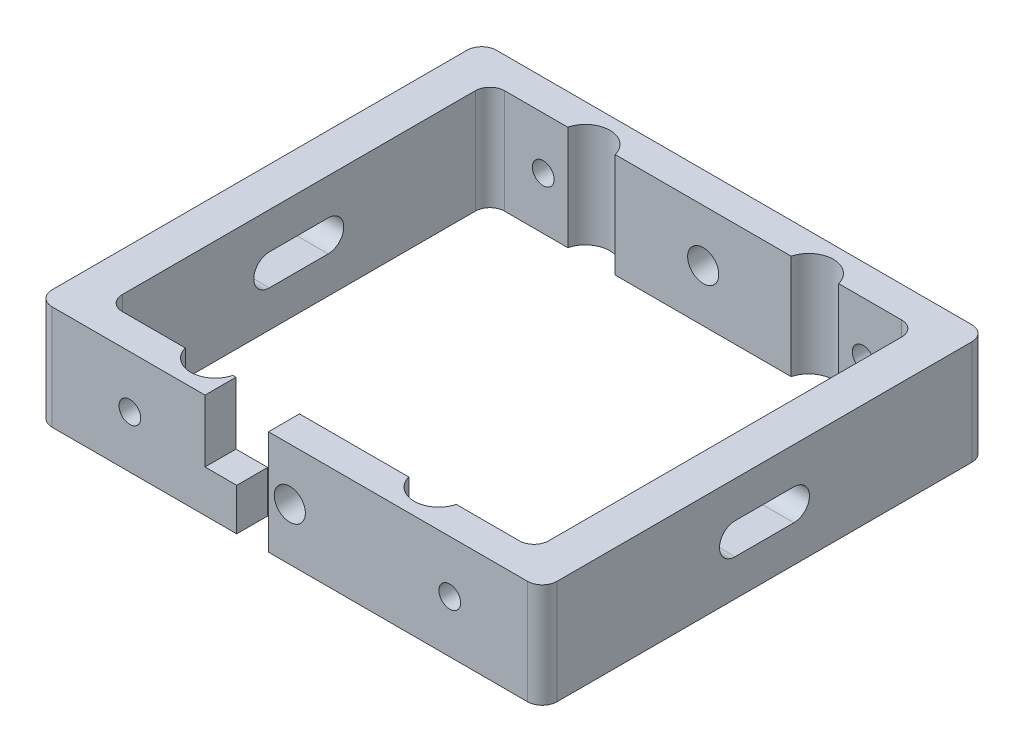
SolidWorks part; units mm, degrees
ref_plane "Front Plane" through (0, 0, 0) normal (0, 0, 1) x (1, 0, 0)
ref_plane "Top Plane" through (0, 0, 0) normal (0, 1, 0) x (1, 0, 0)
ref_plane "Right Plane" through (0, 0, 0) normal (1, 0, 0) x (0, 0, -1)
sketch "Sketch1" plane through (0, 0, 0) normal (0, 1, 0) x (1, 0, 0)
  line L1 (0, 0) -> (60, 0)
  line L2 (0, 0) -> (0, -6.32)
  line L3 (0, -6.32) -> (60, -6.32)
  line L4 (60, 0) -> (60, -6.32)
  dimension "D1" = 60
  dimension "D2" = 6.32
extrude "Boss-Extrude1" add sketch "Sketch1" along normal mid plane 21.28
sketch "Sketch2" plane through (0, 10.64, 0) normal (0, 1, 0) x (1, 0, 0)
  line L0 (0, 0) -> (0, -6.32) construction
  line L1 (0, -6.32) -> (60, -6.32) construction
  line L2 (60, -6.32) -> (60, 0) construction
  circle A0 centre (7.21, 1.25) radius 5
  circle A1 centre (52.79, 1.25) radius 5
  dimension "D1" = 7.21
  dimension "D3" = 7.21
  dimension "D2" = 7.57
  dimension "D4" = 7.57
extrude "Cut-Extrude1" cut sketch "Sketch2" against normal through all
sketch "Sketch3" plane through (60, 0, 0) normal (1, 0, 0) x (0, 0, -1)
  line L1 (-6.32, 10.64) -> (0, 10.64)
  line L2 (-6.32, 10.64) -> (-6.32, -10.64)
  line L3 (-6.32, -10.64) -> (0, -10.64)
  line L4 (0, 10.64) -> (0, -10.64)
extrude "Boss-Extrude2" add sketch "Sketch3" along normal blind 21.5
sketch "Sketch4" plane through (0, 0, 0) normal (-1, 0, 0) x (0, 0, 1)
  line L1 (0, 10.64) -> (6.32, 10.64)
  line L2 (0, 10.64) -> (0, -10.64)
  line L3 (0, -10.64) -> (6.32, -10.64)
  line L4 (6.32, 10.64) -> (6.32, -10.64)
extrude "Boss-Extrude3" add sketch "Sketch4" along normal blind 21.5
sketch "Sketch5" plane through (0, 0, 0) normal (0, 0, -1) x (-1, 0, 0)
  line L5 (-2.3688, -10.64) -> (21.5, -10.64) construction
  line L6 (21.5, 10.64) -> (13.5, 10.64)
  line L7 (21.5, 10.64) -> (21.5, -10.64)
  line L8 (21.5, -10.64) -> (13.5, -10.64)
  line L9 (13.5, 10.64) -> (13.5, -10.64)
  dimension "D1" = 8
extrude "Boss-Extrude6" add sketch "Sketch5" along normal blind 84.33
sketch "Sketch6" plane through (0, 0, 0) normal (0, 0, -1) x (-1, 0, 0)
  line L1 (-81.5, 10.64) -> (-73.5, 10.64)
  line L2 (-81.5, 10.64) -> (-81.5, -10.652)
  line L3 (-81.5, -10.652) -> (-73.5, -10.652)
  line L4 (-73.5, 10.64) -> (-73.5, -10.652)
  dimension "D1" = 8
extrude "Boss-Extrude7" add sketch "Sketch6" along normal blind 84.33
sketch "Sketch7" plane through (73.5, 0, 0) normal (-1, 0, 0) x (0, 0, 1)
  line L0 (-84.33, -10.652) -> (0, -10.652) construction
  line L1 (-84.33, 10.64) -> (-78.01, 10.64)
  line L2 (-84.33, 10.64) -> (-84.33, -10.652)
  line L3 (-84.33, -10.652) -> (-78.01, -10.652)
  line L4 (-78.01, 10.64) -> (-78.01, -10.652)
  dimension "D1" = 6.32
extrude "Boss-Extrude8" add sketch "Sketch7" along normal through all
sketch "Sketch9" plane through (0, 10.64, 0) normal (0, 1, 0) x (1, 0, 0)
  line L0 (-21.5, 84.33) -> (81.5, 84.33) construction
  circle A0 centre (7.21, 76.76) radius 5
  circle A1 centre (52.79, 76.76) radius 5
  dimension "D1" = 7.57
  dimension "D2" = 7.57
  dimension "D3" = 10
extrude "Cut-Extrude2" cut sketch "Sketch9" against normal through all
sketch "Sketch10" plane through (0, 0, -84.33) normal (0, 0, -1) x (-1, 0, 0)
  line L1 (-81.5, -10.64) -> (21.5, -10.64) construction
  line L2 (-30, -10.64) -> (-30, 10.64) construction
  line L3 (21.5, 10.64) -> (-81.5, 10.64) construction
  circle A0 centre (-62.6312, 0.005) radius 2.22
  circle A1 centre (2.6312, 0.005) radius 2.22
  dimension "D1" = 5
  dimension "D2" = 10.645
extrude "Cut-Extrude3" cut sketch "Sketch10" against normal through all
fillet "Fillet1" radius 3 8 edges at (-21.5, 0, 6.32) (81.5, 0, 6.32) (81.5, -0.006, -84.33) (-21.5, -0.006, -84.33) (-13.5, 0, -78.01) (-13.5, 0, 0) (73.5, -0.006, -78.01) (73.5, 0, 0)
sketch "Sketch13" plane through (0, 0, -84.33) normal (0, 0, -1) x (-1, 0, 0)
  line L1 (-78.5, 10.64) -> (-78.5, -10.652) construction
  line L2 (-78.5, -10.64) -> (18.5, -10.64) construction
  circle A0 centre (-30, 0.005) radius 3.175
  dimension "D1" = 48.5
  dimension "D3" = 6.35
  dimension "D2" = 10.645
extrude "Cut-Extrude4" cut sketch "Sketch13" against normal through all
sketch "Sketch16" plane through (0, -10.652, 0) normal (0, -1, 0) x (1, 0, 0)
  line L6 (78.5, -84.33) -> (-18.5, -84.33) construction
  line L7 (25.5729, -84.33) -> (12.6189, -84.33)
  line L8 (25.5729, -84.33) -> (25.5729, -78.01)
  line L9 (25.5729, -78.01) -> (12.6189, -78.01)
  line L10 (12.6189, -84.33) -> (12.6189, -78.01)
  line L11 (12.0512, -78.01) -> (47.9488, -78.01) construction
  dimension "D1" = 12.954
extrude "Cut-Extrude6" [suppressed] cut sketch "Sketch16" against normal mid plane 25.4
sketch "Sketch17" plane through (0, 10.64, 0) normal (0, 1, 0) x (1, 0, 0)
  line L1 (12.6964, 0.5862) -> (25.6504, 0.5862)
  line L2 (12.6964, 0.5862) -> (12.6964, -6.4457)
  line L3 (12.6964, -6.4457) -> (25.6504, -6.4457)
  line L4 (25.6504, 0.5862) -> (25.6504, -6.4457)
  dimension "D1" = 12.954
extrude "Cut-Extrude7" cut sketch "Sketch17" against normal mid plane 25.4
sketch "Sketch18" plane through (0, 0, 6.32) normal (0, 0, 1) x (1, 0, 0)
  line L0 (12.6964, -2.06) -> (25.6504, -2.06) construction
  line L1 (19.1734, -2.06) -> (25.6504, -2.06)
  line L2 (19.1734, -2.06) -> (19.1734, -10.64)
  line L3 (19.1734, -10.64) -> (25.6504, -10.64)
  line L4 (25.6504, -2.06) -> (25.6504, -10.64)
  line L5 (-18.5, -10.64) -> (78.5, -10.64) construction
extrude "Cut-Extrude8" cut sketch "Sketch18" against normal up to next
sketch "Sketch19" plane through (-21.5, 0, 0) normal (-1, 0, 0) x (0, 0, 1)
  line L0 (-81.33, 10.64) -> (-81.33, -10.652) construction
  line L1 (-45.005, 3.175) -> (-33.005, 3.175)
  line L2 (-45.005, -3.175) -> (-33.005, -3.175)
  arc A1 (-45.005, 3.175) -> (-45.005, -3.175) centre (-45.005, 0) ccw
  arc A2 (-33.005, -3.175) -> (-33.005, 3.175) centre (-33.005, 0) ccw
  dimension "D1" = 36.325
  dimension "D2" = 12
extrude "Cut-Extrude9" cut sketch "Sketch19" against normal through all
